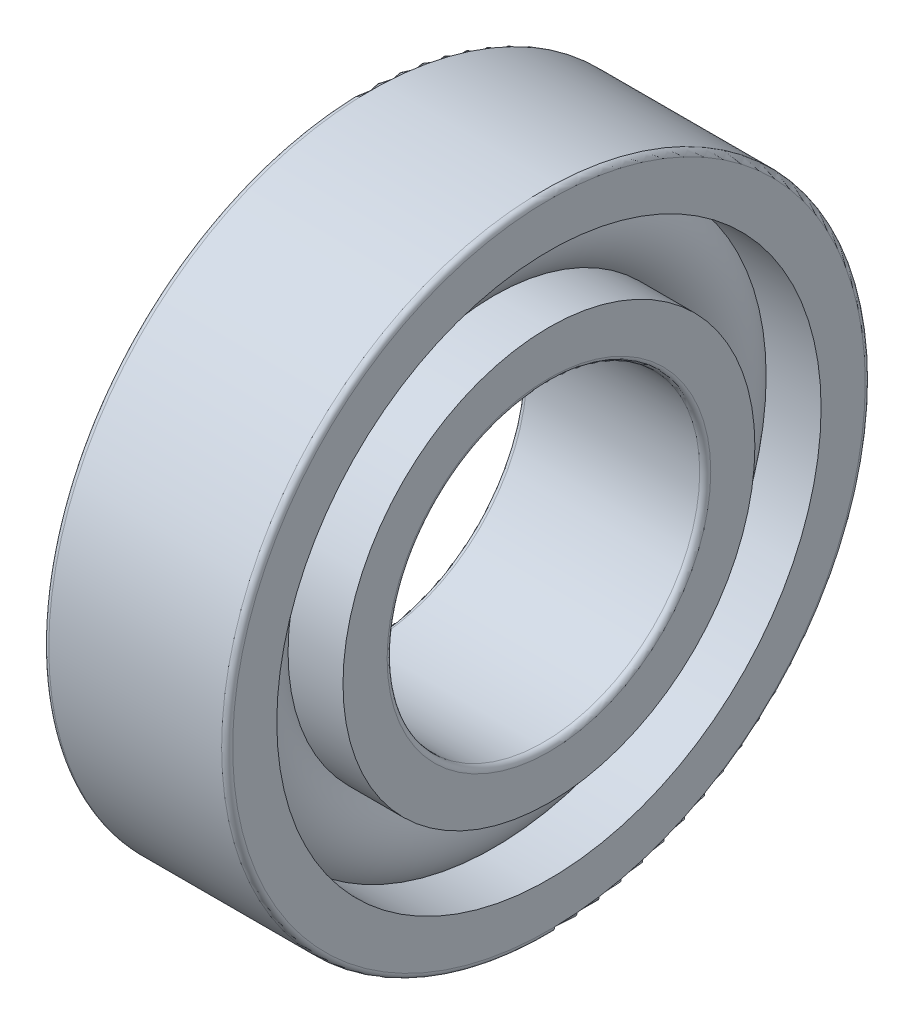
SolidWorks part; units mm, degrees
ref_plane "Plane1" through (0, 0, 0) normal (0, 0, 1) x (1, 0, 0)
ref_plane "Plane2" through (0, 0, 0) normal (0, 1, 0) x (1, 0, 0)
ref_plane "Plane3" through (0, 0, 0) normal (1, 0, 0) x (0, 0, -1)
sketch "Clipboard" plane through (0, 0, 0) normal (0, 0, 1) x (1, 0, 0)
  line L0 (-10, 0) -> (10, 0) construction
  line L1 (0, 0) -> (22.3471, -0.7804)
  line L2 (0, 0) -> (12.9921, 0.4537)
  line L3 (0, 0) -> (22.3471, -0.7804)
  line L4 (0, 0) -> (-22.3573, -0.3902)
  dimension "BallCLRad" = 13
  dimension "Count" = 2
  dimension "Show_count" = 2
  dimension "Max_count" = 2
  dimension "Min_count" = 1
sketch "CagSpiSke" plane through (0, 0, 0) normal (0, 0, 1) x (1, 0, 0)
  line L0 (0.27, 12.55) -> (0.27, 13.45)
  line L1 (0.27, 13.45) -> (-0.27, 13.45)
  line L2 (-0.27, 13.45) -> (-0.27, 12.55)
  line L3 (-0.27, 12.55) -> (0.27, 12.55)
  line L4 (-20.6375, 0) -> (20.6375, 0) construction
  line L5 (0, 0) -> (0, 23.7692) construction
  dimension "Thickness" = 0.54
  dimension "OD" = 26.9
  dimension "ID" = 25.1
revolve "CageSpine" add sketch "CagSpiSke" angle 0.001 about L4 reverse direction yes
ref_axis "Axis1" through (-50, 0, 0) along (1, 0, 0)
sketch "CagBalSke" plane through (0, 0, 0) normal (0, 0, 1) x (1, 0, 0)
  line L0 (-2.97, 13) -> (2.97, 13)
  line L1 (-1.905, 13) -> (1.905, 13) construction
  line L2 (-10, 0) -> (10, 0) construction
  line L3 (0, 0) -> (0, 24) construction
  arc A0 (2.97, 13) -> (-2.97, 13) centre (0, 13) cw
  dimension "CageWallOD" = 5.94
  dimension "BallCLRad" = 13
revolve "CageBall" [suppressed] add sketch "CagBalSke" angle 360 about L1 reverse direction yes
pattern_circular "CageBalls" [suppressed] count 2 every 180 about axis through (-50, 0, 0) along (1, 0, 0)
sketch "CagTrmODSke" plane through (0, 0, 0) normal (0, 0, 1) x (1, 0, 0)
  line L0 (2.971, 13.45) -> (2.971, 15.971)
  line L1 (2.971, 15.971) -> (-2.971, 15.971)
  line L2 (-2.971, 15.971) -> (-2.971, 13.45)
  line L3 (-2.971, 13.45) -> (2.971, 13.45)
  line L4 (-20.6375, 0) -> (20.6375, 0) construction
  line L5 (0, 0) -> (0, 25) construction
  dimension "Width" = 5.942
  dimension "ID" = 26.9
  dimension "OD" = 31.942
revolve "CageTrimOD" [suppressed] cut sketch "CagTrmODSke" angle 360 about L4 reverse direction yes
sketch "CagTrmIDSke" plane through (0, 0, 0) normal (0, 0, 1) x (1, 0, 0)
  line L0 (2.971, 10.031) -> (2.971, 12.55)
  line L1 (2.971, 12.55) -> (-2.971, 12.55)
  line L2 (-2.971, 12.55) -> (-2.971, 10.031)
  line L3 (-2.971, 10.031) -> (2.971, 10.031)
  line L4 (-20.6375, 0) -> (20.6375, 0) construction
  line L5 (0, 0) -> (0, 25) construction
  dimension "ID" = 20.062
  dimension "OD" = 25.1
  dimension "Width" = 5.942
revolve "CageTrimID" [suppressed] cut sketch "CagTrmIDSke" angle 360 about L4 reverse direction yes
sketch "BalSimSke" plane through (0, 0, 0) normal (0, 0, 1) x (1, 0, 0)
  line L0 (-10, 0) -> (10, 0) construction
  line L1 (-10, 13) -> (10, 13) construction
  line L2 (0, 0) -> (0, 23) construction
  circle A0 centre (0, 13) radius 2.7
  dimension "Ball_diameter" = 5.4
  dimension "BallCLRad" = 13
revolve "BallsSimplified" add sketch "BalSimSke" angle 360 about L0
sketch "BalDetSke" plane through (0, 0, 0) normal (0, 0, 1) x (1, 0, 0)
  line L0 (-2.7, 13) -> (2.7, 13)
  line L1 (-1.905, 13) -> (1.905, 13) construction
  line L2 (0, 0) -> (0, 25) construction
  arc A0 (2.7, 13) -> (-2.7, 13) centre (0, 13) cw
  dimension "Ball_diameter" = 5.4
  dimension "BallCLRad" = 13
revolve "BallDetailed" [suppressed] add sketch "BalDetSke" angle 360 about L1 reverse direction yes
sketch "InnRacSke" plane through (0, 0, 0) normal (0, 0, 1) x (1, 0, 0)
  line L0 (-1.9788, 11.2) -> (-5, 11.2)
  line L1 (-5, 11.2) -> (-5, 8.8)
  line L2 (-4.7, 8.5) -> (4.7, 8.5)
  line L3 (5, 8.8) -> (5, 11.2)
  line L4 (5, 11.2) -> (1.9788, 11.2)
  line L5 (-20.6375, 0) -> (20.6375, 0) construction
  line L6 (0, 0) -> (0, 30) construction
  arc A0 (-5, 8.8) -> (-4.7, 8.5) centre (-4.7, 8.8) ccw
  arc A1 (4.7, 8.5) -> (5, 8.8) centre (4.7, 8.8) ccw
  arc A2 (1.9788, 11.2) -> (-1.9788, 11.2) centre (0, 13) cw
  dimension "Fillet_radius" = 0.3
  dimension "Ball_diameter" = 5.35
  dimension "ID" = 17
  dimension "OD" = 22.4
  dimension "Width" = 10
  dimension "BallCLRad" = 13
revolve "InnerRace" add sketch "InnRacSke" angle 360 about L5 reverse direction yes
sketch "OutRacSke" plane through (0, 0, 0) normal (0, 0, 1) x (1, 0, 0)
  line L0 (-1.9788, 14.8) -> (-5, 14.8)
  line L1 (-5, 14.8) -> (-5, 17.2)
  line L2 (-4.7, 17.5) -> (4.7, 17.5)
  line L3 (5, 17.2) -> (5, 14.8)
  line L4 (5, 14.8) -> (1.9788, 14.8)
  line L5 (-20.6375, 0) -> (20.6375, 0) construction
  line L6 (0, 0) -> (0, 30) construction
  arc A0 (-5, 17.2) -> (-4.7, 17.5) centre (-4.7, 17.2) cw
  arc A1 (4.7, 17.5) -> (5, 17.2) centre (4.7, 17.2) cw
  arc A2 (1.9788, 14.8) -> (-1.9788, 14.8) centre (0, 13) ccw
  dimension "Fillet_radius" = 0.3
  dimension "Ball_diameter" = 5.35
  dimension "OD" = 35
  dimension "ID" = 29.6
  dimension "Width" = 10
  dimension "BallCLRad" = 13
revolve "OuterRace" add sketch "OutRacSke" angle 360 about L5 reverse direction yes
pattern_circular "BallsDetailed" [suppressed] count 2 every 180 about axis through (-50, 0, 0) along (1, 0, 0)
equation "\"BallCLRad@Clipboard\" = ( \"OD@OutRacSke\" + \"ID@InnRacSke\" ) / 4"
equation "\"BallCLRad@BalSimSke\" = \"BallCLRad@Clipboard\""
equation "\"BallCLRad@BalDetSke\" = \"BallCLRad@Clipboard\""
equation "\"BallCLRad@InnRacSke\" = \"BallCLRad@Clipboard\""
equation "\"BallCLRad@OutRacSke\" = \"BallCLRad@Clipboard\""
equation "\"Ball_diameter@InnRacSke\" = \"Ball_diameter@BalDetSke\" - 0.05"
equation "\"Ball_diameter@OutRacSke\" = \"Ball_diameter@BalDetSke\" - 0.05"
equation "\"Ball_diameter@BalSimSke\" = \"Ball_diameter@BalDetSke\""
equation "\"Width@OutRacSke\" = \"Width@InnRacSke\""
equation "\"Fillet_radius@OutRacSke\" = \"Fillet_radius@InnRacSke\""
equation "\"Max_count@Clipboard\" = int( 3.14159265 / atn(( \"Ball_diameter@BalDetSke\" / 2) / sqr( \"BallCLRad@Clipboard\"  *  \"BallCLRad@Clipboard\" - ( \"Ball_diameter@BalDetSke\" / 2) *  ( \"Ball_diameter@BalDetSke\" / 2))))"
equation "\"Max_count@Clipboard\" = ((sgn( \"Max_count@Clipboard\" - \"Count@Clipboard\" )-1)*( \"Max_count@Clipboard\" - \"Count@Clipboard\" ))/-2+ \"Count@Clipboard\""
equation "\"Count@BallsDetailed\" = int( \"Show_count@Clipboard\" ) "
equation "\"Count@BallsDetailed\" = ((sgn( \"Count@BallsDetailed\" - \"Max_count@Clipboard\" )-1)*( \"Count@BallsDetailed\" - \"Max_count@Clipboard\" ))/-2+ \"Max_count@Clipboard\""
equation "\"Count@BallsDetailed\" = ((sgn( \"Count@BallsDetailed\" - \"Min_count@Clipboard\" )+1)*( \"Count@BallsDetailed\" - \"Min_count@Clipboard\"))/2 +\"Min_count@Clipboard\""
equation "\"Angle@BallsDetailed\" = 360.0 / \"Max_count@Clipboard\""
equation "\"BallCLRad@CagBalSke\" = \"BallCLRad@Clipboard\""
equation "\"Count@CageBalls\" = \"Count@BallsDetailed\""
equation "\"Angle@CageBalls\" = \"Angle@BallsDetailed\""
equation "\"Angle@CageSpine\" =  \"Angle@CageBalls\" * ( \"Count@CageBalls\" -1 + int( \"Count@CageBalls\" / \"Max_count@Clipboard\" ) )  + 0.001 -  int( \"Count@CageBalls\" / \"Max_count@Clipboard\" ) * 0.001"
equation "\"Angle@CageSpine\" =  \"Angle@CageSpine\" * int( \"Min_count@Clipboard\" / 2) + int(1 / \"Min_count@Clipboard\")  * 0.001"
equation "\"CageWallOD@CagBalSke\" =  \"Ball_diameter@BalDetSke\" * 1.1"
equation "\"Thickness@CagSpiSke\" =  \"Ball_diameter@BalDetSke\" * 0.1"
equation "\"OD@CagTrmODSke\" = \"BallCLRad@Clipboard\" * 2 + \"CageWallOD@CagBalSke\" + 0.002"
equation "\"ID@CagTrmODSke\" = \"BallCLRad@Clipboard\" * 2 + \"Ball_diameter@BalDetSke\" / 6"
equation "\"OD@CagTrmIDSke\" = \"BallCLRad@Clipboard\" * 2 - \"Ball_diameter@BalDetSke\" / 6"
equation "\"ID@CagTrmIDSke\" = \"BallCLRad@Clipboard\" * 2 - \"CageWallOD@CagBalSke\" + 0.002"
equation "\"OD@CagSpiSke\" = \"ID@CagTrmODSke\""
equation "\"ID@CagSpiSke\" = \"OD@CagTrmIDSke\""
equation "\"Width@CagTrmODSke\" = \"CageWallOD@CagBalSke\" + 0.002"
equation "\"Width@CagTrmIDSke\" = \"CageWallOD@CagBalSke\" + 0.002"
